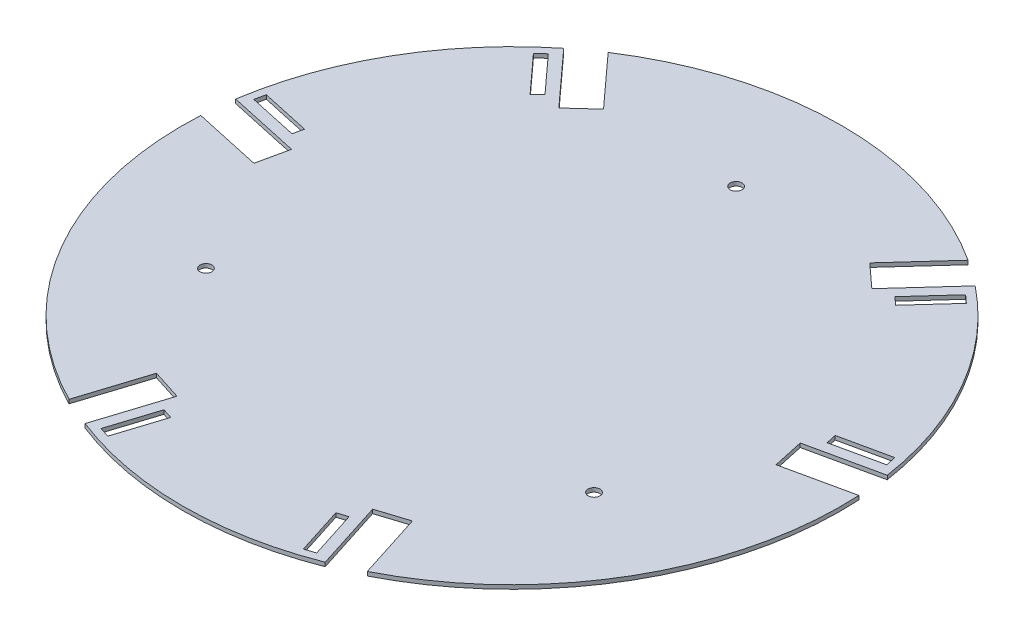
SolidWorks part; units mm, degrees
ref_plane "Front Plane" through (0, 0, 0) normal (0, 0, 1) x (1, 0, 0)
ref_plane "Top Plane" through (0, 0, 0) normal (0, 1, 0) x (1, 0, 0)
ref_plane "Right Plane" through (0, 0, 0) normal (1, 0, 0) x (0, 0, -1)
sketch "Sketch2" plane through (0, 0, 0) normal (0, 1, 0) x (1, 0, 0)
  circle A0 centre (0, 0) radius 125
  dimension "D1" = 250
extrude "Boss-Extrude1" add sketch "Sketch2" along normal blind 1.5 contours A0
sketch "Sketch3" plane through (0, 1.5, 0) normal (0, 1, 0) x (1, 0, 0)
  line L0 (0, 0) -> (-38, -119.084) construction
  line L1 (-270.1917, -358.6733) -> (-267.1917, -358.6733)
  line L2 (-270.1917, -358.6733) -> (-270.1917, -377.6733)
  line L3 (-270.1917, -377.6733) -> (-267.1917, -377.6733)
  line L4 (-267.1917, -358.6733) -> (-267.1917, -377.6733)
  line L9 (-38, -119.084) -> (38, -119.084) construction
  line L10 (0, 0) -> (0, -293.8403) construction
  line L11 (31.312, -98.1252) -> (35.1227, -96.9092)
  line L12 (37.088, -116.226) -> (40.8987, -115.01)
  line L14 (37.088, -116.226) -> (31.312, -98.1252)
  line L15 (40.8987, -115.01) -> (35.1227, -96.9092)
  line L17 (-38, -119.084) -> (-37.088, -116.226) construction
  line L19 (-37.088, -116.226) -> (-31.312, -98.1252)
  line L20 (-37.088, -116.226) -> (-40.8987, -115.01)
  line L21 (-31.312, -98.1252) -> (-35.1227, -96.9092)
  line L22 (-40.8987, -115.01) -> (-35.1227, -96.9092)
  line L52 (-82.1107, 90.2321) -> (-69.3229, 76.1796)
  line L53 (-82.1107, 90.2321) -> (-79.1522, 92.9243)
  line L54 (-79.1522, 92.9243) -> (-66.3645, 78.8717)
  line L55 (-69.3229, 76.1796) -> (-66.3645, 78.8717)
  line L56 (-100.6349, 21.9456) -> (-101.4872, 18.0375)
  line L57 (-120.0509, 22.0857) -> (-101.4872, 18.0375)
  line L58 (-119.1987, 25.9938) -> (-120.0509, 22.0857)
  line L59 (-119.1987, 25.9938) -> (-100.6349, 21.9456)
  line L60 (119.1987, 25.9938) -> (100.6349, 21.9456)
  line L61 (119.1987, 25.9938) -> (120.0509, 22.0857)
  line L62 (120.0509, 22.0857) -> (101.4872, 18.0375)
  line L63 (100.6349, 21.9456) -> (101.4872, 18.0375)
  line L64 (69.3229, 76.1796) -> (66.3645, 78.8717)
  line L65 (79.1522, 92.9243) -> (66.3645, 78.8717)
  line L66 (82.1107, 90.2321) -> (79.1522, 92.9243)
  line L67 (82.1107, 90.2321) -> (69.3229, 76.1796)
  circle A1 centre (0, 0) radius 125 construction
  point P18 (0, 0)
  point P38 (-15.7426, 25.0605)
  point P39 (0, 0)
  point P46 (-7.6333, 12.5317)
  dimension "D1" = 3
  dimension "D2" = 19
  dimension "D3" = 76
  dimension "D4" = 3
  dimension "D5" = 3
  dimension "D7" = 4
  dimension "D8" = 19
extrude "Cut-Extrude1" cut sketch "Sketch3" against normal through all
sketch "Sketch4" plane through (0, 1.5, 0) normal (0, 1, 0) x (1, 0, 0)
  circle A3 centre (0, 85) radius 2.25
  circle A4 centre (73.6122, -42.5) radius 2.25
  circle A5 centre (-73.6122, -42.5) radius 2.25
  point P8 (0, 0)
  dimension "D1" = 85
  dimension "D2" = 3
  dimension "D3" = 4.5
extrude "Cut-Extrude2" cut sketch "Sketch4" against normal through all
sketch "Sketch6" plane through (0, 1.5, 0) normal (0, 1, 0) x (1, 0, 0)
  line L0 (-40.8987, -115.01) -> (-44.7094, -113.794) construction
  line L1 (-35.1227, -96.9092) -> (-40.8987, -115.01) construction
  line L2 (0, 0) -> (0, -140.3527) construction
  line L3 (-44.7094, -113.794) -> (-55.9925, -149.153) construction
  line L4 (-55.9925, -149.153) -> (-67.4246, -145.505)
  line L5 (-55.9925, -149.153) -> (-37.1094, -89.9772)
  line L6 (-67.4246, -145.505) -> (-48.5414, -86.3292)
  line L7 (-37.1094, -89.9772) -> (-48.5414, -86.3292)
  line L8 (67.4246, -145.505) -> (48.5414, -86.3292)
  line L9 (37.1094, -89.9772) -> (48.5414, -86.3292)
  line L10 (55.9925, -149.153) -> (37.1094, -89.9772)
  line L11 (55.9925, -149.153) -> (67.4246, -145.505)
  dimension "D1" = 12
  dimension "D2" = 25
  dimension "D3" = 4
extrude "Cut-Extrude5" cut sketch "Sketch6" against normal through all
pattern_circular "CirPattern2" count 3 over 360 about axis through (0, 1.5, 0) along (0, 1, 0) of "Cut-Extrude5"
